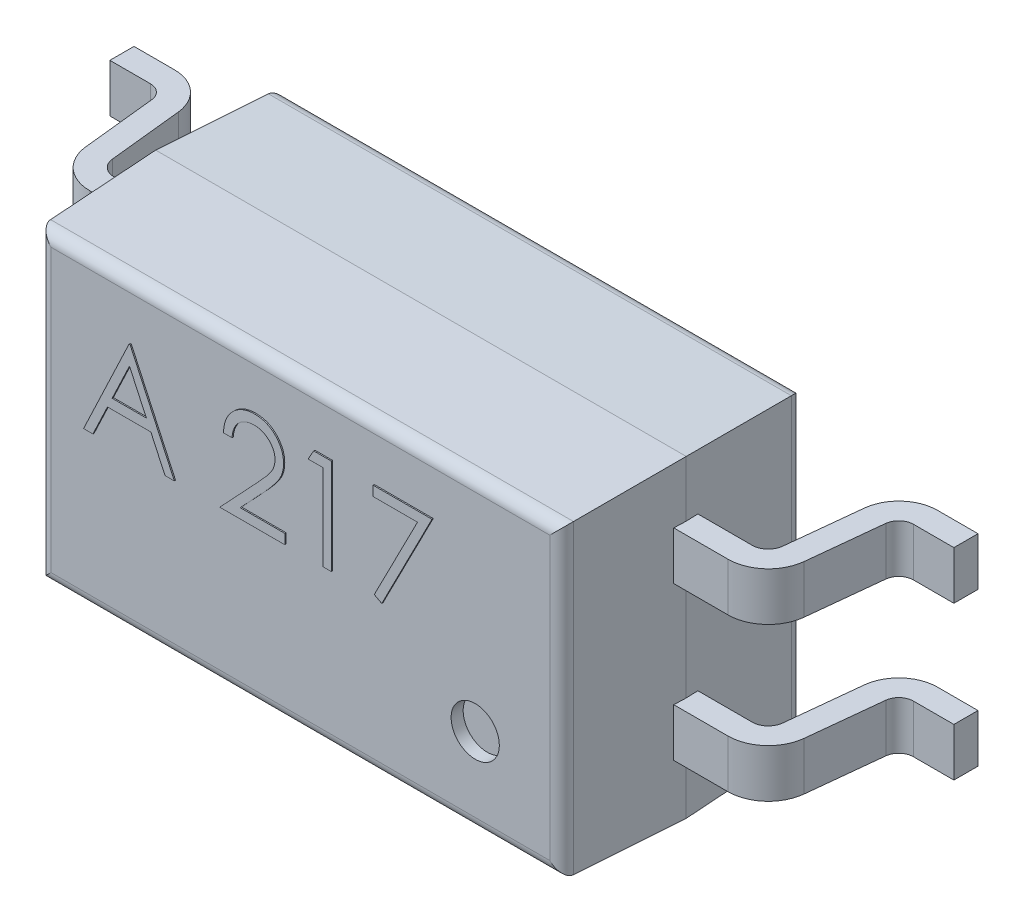
SolidWorks part; units mm, degrees
ref_plane "Plan de face" through (0, 0, 0) normal (0, 0, 1) x (1, 0, 0)
ref_plane "Plan de dessus" through (0, 0, 0) normal (0, 1, 0) x (1, 0, 0)
ref_plane "Plan de droite" through (0, 0, 0) normal (1, 0, 0) x (0, 0, -1)
sketch "Esquisse1" plane through (0, 0, 0) normal (0, 0, 1) x (1, 0, 0)
  line L1 (4.4, 2.6) -> (0, 2.6)
  line L2 (4.4, 2.6) -> (4.4, 0)
  line L3 (4.4, 0) -> (0, 0)
  line L4 (0, 2.6) -> (0, 0)
  dimension "D1" = 2.6
  dimension "D2" = 4.4
extrude "Boss.-Extru.1" add sketch "Esquisse1" along normal blind 2
chamfer "Chanfrein1" distance 1 angle 2 4 edges at (2.2, 0, 2) (0, 1.3, 2) (4.4, 1.3, 2) (2.2, 2.6, 2) first distance on face at (2.2, 0, 1) first distance on face at (0, 1.3, 1) first distance on face at (4.4, 1.3, 1) first distance on face at (2.2, 2.6, 1)
chamfer "Chanfrein2" distance 1 angle 2 4 edges at (2.2, 0, 0) (4.4, 1.3, 0) (2.2, 2.6, 0) (0, 1.3, 0) first distance on face at (2.2, 0, 0.5) first distance on face at (4.4, 1.3, 0.5) first distance on face at (2.2, 2.6, 0.5) first distance on face at (0, 1.3, 0.5)
sketch "Esquisse2" plane through (0, 0, 2) normal (0, 0, 1) x (1, 0, 0)
  line L0 (4.4, 2.6) -> (4.4, 0) construction
  line L1 (4.4, 0) -> (0, 0) construction
  circle A0 centre (3.65, 0.75) radius 0.2
  dimension "D1" = 0.4
  dimension "D2" = 0.75
  dimension "D3" = 0.75
extrude "Enlèv. mat.-Extru.1" cut sketch "Esquisse2" against normal blind 0.1
sketch "Esquisse3" plane through (0, 0, 2) normal (0, 0, 1) x (1, 0, 0)
  line L0 (4.4, 2.6) -> (4.737, 2.6) construction
  line L1 (4.6992, 2.0715) -> (4.3992, 2.0715)
  line L2 (4.6992, 2.0715) -> (4.6992, 1.7715)
  line L3 (4.6992, 1.7715) -> (4.3992, 1.7715)
  line L4 (4.3992, 2.0715) -> (4.3992, 1.7715)
  line L5 (-0.2996, 2.0715) -> (0.0004, 2.0715)
  line L6 (-0.2996, 2.0715) -> (-0.2996, 1.7715)
  line L7 (-0.2996, 1.7715) -> (0.0004, 1.7715)
  line L8 (0.0004, 2.0715) -> (0.0004, 1.7715)
  line L9 (4.737, 2.6) -> (4.737, 2.1691) construction
  line L10 (4.737, 2.1691) -> (4.737, 1.935) construction
  line L11 (4.737, 0.8991) -> (4.737, 0.665) construction
  line L12 (4.737, 0.665) -> (4.737, 0.4309) construction
  line L13 (4.737, 0.4309) -> (4.737, 0) construction
  line L14 (4.4, 0) -> (4.737, 0) construction
  line L16 (4.737, 1.935) -> (4.737, 1.7009) construction
  line L17 (4.737, 1.7009) -> (4.737, 0.8991) construction
  line L18 (4.4, 1.3) -> (4.737, 1.3) construction
  line L19 (4.4, 2.6) -> (4.4, 0) construction
  dimension "D1" = 0.3
  dimension "D2" = 0.3
  dimension "D3" = 0.3
  dimension "D4" = 0.3
  dimension "D5" = 1.27
extrude "Enlèv. mat.-Extru.2" cut sketch "Esquisse3" against normal through all
sketch "Esquisse4" plane through (4.3992, 0, 0) normal (1, 0, 0) x (0, 0, -1)
  line L0 (-1.1, 2.135) -> (-1, 2.135)
  line L1 (-1, 2.6) -> (-1, 2.0715) construction
  line L2 (-1.1, 2.135) -> (-1.1, 1.735)
  line L3 (-1.1, 1.735) -> (-0.9, 1.735)
  line L4 (-0.9, 2.135) -> (-0.9, 1.735)
  line L5 (-1.1, 0.865) -> (-0.9, 0.865)
  line L6 (-1.1, 0.865) -> (-1.1, 0.465)
  line L7 (-1.1, 0.465) -> (-0.9, 0.465)
  line L8 (-0.9, 0.865) -> (-0.9, 0.465)
  line L9 (-1, 2.135) -> (-0.9, 2.135)
  line L10 (-1.1, 1.735) -> (-1.1, 1.3) construction
  line L11 (-1.1, 1.3) -> (-1.1, 0.865) construction
  line L12 (-2, 1.3) -> (-1.1, 1.3) construction
  line L13 (-2, 0.0349) -> (-2, 2.5651) construction
  line L14 (-1.1, 0.865) -> (-0.9, 0.465) construction
  line L15 (-1.1, 1.735) -> (-0.9, 2.135) construction
  line L16 (-1.1, 2.135) -> (-1, 1.935) construction
  line L17 (-1.1, 0.465) -> (-1, 0.665) construction
  dimension "D1" = 0.4
  dimension "D2" = 0.2
  dimension "D3" = 1.27
extrude "Boss.-Extru.2" add sketch "Esquisse4" along normal up to vertex (0.0008 mm away) and the other way up to vertex (4.3992 mm away) up to point (4.4, 1.7715, 1) other way up to point (0, 0, 1)
sketch "Esquisse5" plane through (0, 0, 0) normal (-1, 0, 0) x (0, 0, 1)
  line L0 (1.1, 1.735) -> (1, 1.735) construction
  line L1 (1.1, 0.465) -> (-0.12, 0.465)
  line L2 (1.1, 0.465) -> (1.1, 0.865)
  line L3 (1.1, 0.865) -> (-0.12, 0.865)
  line L4 (-0.12, 0.465) -> (-0.12, 0.865)
  line L5 (1.1, 1.735) -> (-0.12, 1.735)
  line L6 (1.1, 1.735) -> (1.1, 2.135)
  line L7 (1.1, 2.135) -> (-0.12, 2.135)
  line L8 (-0.12, 1.735) -> (-0.12, 2.135)
  line L9 (1.1, 2.135) -> (1.1, 1.735) construction
  line L10 (1, 2.135) -> (1.1, 2.135) construction
  line L11 (0.9, 0.865) -> (1, 0.865) construction
  line L12 (0, 0.0349) -> (0, 2.5651) construction
  dimension "D1" = 0.12
extrude "Boss.-Extru.3" add sketch "Esquisse5" along normal blind 1.3
sketch "Esquisse6" plane through (4.4, 0, 0) normal (1, 0, 0) x (0, 0, -1)
  line L1 (-1.1, 2.135) -> (0.12, 2.135)
  line L2 (-1.1, 2.135) -> (-1.1, 1.735)
  line L3 (-1.1, 1.735) -> (0.12, 1.735)
  line L4 (0.12, 2.135) -> (0.12, 1.735)
  line L5 (-1.1, 0.865) -> (0.12, 0.865)
  line L6 (-1.1, 0.865) -> (-1.1, 0.465)
  line L7 (-1.1, 0.465) -> (0.12, 0.465)
  line L8 (0.12, 0.865) -> (0.12, 0.465)
extrude "Boss.-Extru.4" add sketch "Esquisse6" along normal blind 1.3
sketch "Esquisse7" plane through (0, 0.465, 0) normal (0, -1, 0) x (1, 0, 0)
  line L0 (2.2, 0) -> (2.2, 2) construction
  line L1 (4.3651, 0) -> (0.0349, 0) construction
  line L2 (0.0349, 2) -> (4.3651, 2) construction
  line L3 (0, 0.9) -> (-0.4465, 0.9)
  line L4 (-1.3, 0.08) -> (-0.9642, 0.08)
  line L5 (-1.3, -0.12) -> (-1.3, 1.1) construction
  line L6 (-1.3, -0.12) -> (0, -0.12) construction
  line L7 (0.0035, 1.1) -> (-1.3, 1.1) construction
  line L8 (-0.5799, 0.78) -> (-0.6448, 0.1674)
  line L9 (-0.7788, 0.801) -> (-0.8437, 0.1885)
  line L10 (-1.3, 0.08) -> (-1.3, 1.1)
  line L11 (-1.3, 1.1) -> (-0.4465, 1.1)
  line L12 (0, 0.9) -> (0, -0.12)
  line L13 (0, -0.12) -> (-0.9642, -0.12)
  line L14 (-0.7788, 0.801) -> (-0.5799, 0.78) construction
  line L15 (-0.8437, 0.1885) -> (-0.6448, 0.1674) construction
  line L16 (5.2437, 0.1885) -> (5.0448, 0.1674) construction
  line L17 (5.1788, 0.801) -> (4.9799, 0.78) construction
  line L18 (4.4, -0.12) -> (5.3642, -0.12)
  line L19 (4.4, 0.9) -> (4.4, -0.12)
  line L20 (5.7, 1.1) -> (4.8465, 1.1)
  line L21 (5.7, 0.08) -> (5.7, 1.1)
  line L22 (5.1788, 0.801) -> (5.2437, 0.1885)
  line L23 (4.9799, 0.78) -> (5.0448, 0.1674)
  line L24 (5.7, 0.08) -> (5.3642, 0.08)
  line L25 (4.4, 0.9) -> (4.8465, 0.9)
  arc A0 (-0.4465, 1.1) -> (-0.7788, 0.801) centre (-0.4465, 0.7658) ccw
  arc A1 (-0.4465, 0.9) -> (-0.5799, 0.78) centre (-0.4465, 0.7658) ccw
  arc A2 (-0.8437, 0.1885) -> (-0.9642, 0.08) centre (-0.9642, 0.2012) cw
  arc A3 (-0.6448, 0.1674) -> (-0.9642, -0.12) centre (-0.9642, 0.2012) cw
  arc A4 (5.0448, 0.1674) -> (5.3642, -0.12) centre (5.3642, 0.2012) ccw
  arc A5 (5.2437, 0.1885) -> (5.3642, 0.08) centre (5.3642, 0.2012) ccw
  arc A6 (4.8465, 0.9) -> (4.9799, 0.78) centre (4.8465, 0.7658) cw
  arc A7 (4.8465, 1.1) -> (5.1788, 0.801) centre (4.8465, 0.7658) cw
  dimension "D1" = 0.2
  dimension "D2" = 0.45
  dimension "D3" = 0.2
extrude "Enlèv. mat.-Extru.3" cut sketch "Esquisse7" against normal through all
fillet "Congé1" radius 0.1 4 edges at (4.3651, 1.3, 2) (2.2, 0.0349, 2) (0.0349, 1.3, 2) (2.2, 2.5651, 2)
fillet "Congé2" radius 0.1 4 edges at (4.3651, 1.3, 0) (2.2, 2.5651, 0) (0.0349, 1.3, 0) (2.2, 0.0349, 0)
sketch "Esquisse8" plane through (0, 0, 2) normal (0, 0, 1) x (1, 0, 0)
  text T0 "A 217" font "Century Gothic" height in points 3
extrude "Boss.-Extru.5" add sketch "Esquisse8" along normal blind 0.01
